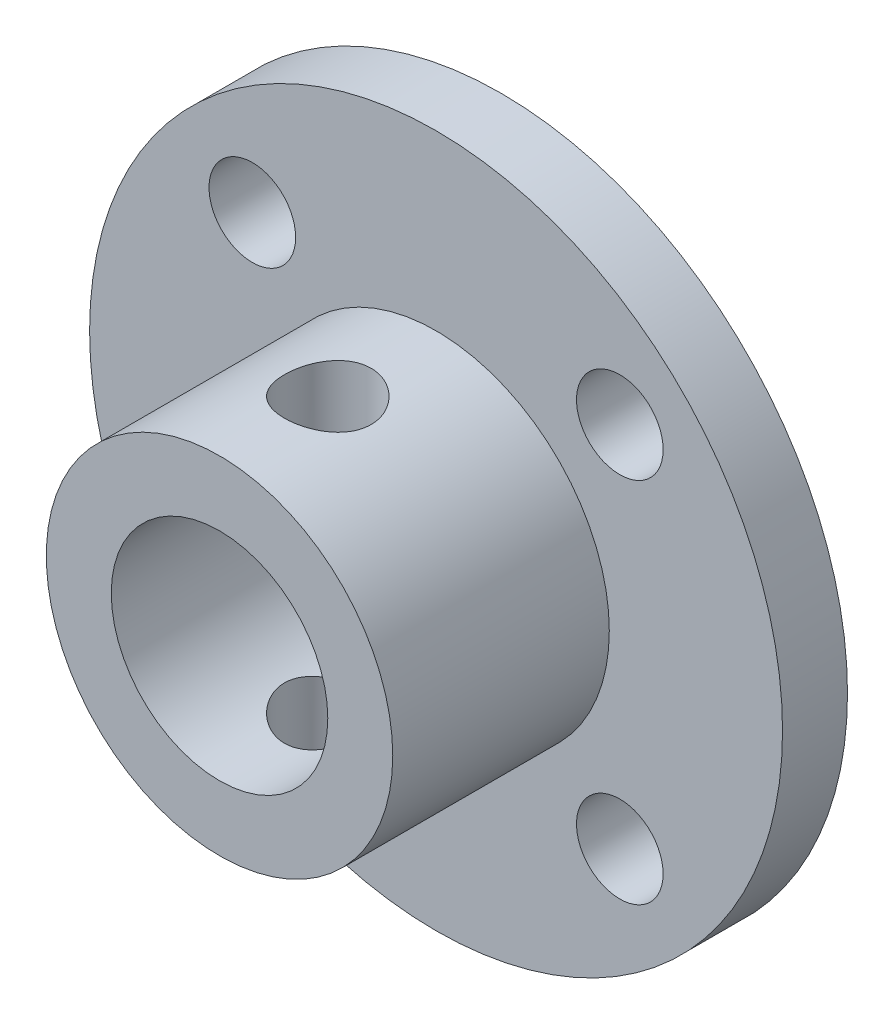
SolidWorks part; units mm, degrees
ref_plane "前视基准面" through (0, 0, 0) normal (0, 0, 1) x (1, 0, 0)
ref_plane "上视基准面" through (0, 0, 0) normal (0, 1, 0) x (1, 0, 0)
ref_plane "右视基准面" through (0, 0, 0) normal (1, 0, 0) x (0, 0, -1)
sketch "草图2" plane through (0, 0, 0) normal (0, 0, 1) x (1, 0, 0)
  circle A0 centre (0, 0) radius 16
  circle A1 centre (0, 0) radius 12 construction
  circle A2 centre (0, 0) radius 5
  circle A3 centre (8.4853, -8.4853) radius 2
  circle A4 centre (-8.4853, -8.4853) radius 2
  circle A5 centre (-8.4853, 8.4853) radius 2
  circle A6 centre (8.4853, 8.4853) radius 2
  dimension "D1" = 24
  dimension "D2" = 10
  dimension "D3" = 4
  dimension "D5" = 32
  dimension "D4" = 4
extrude "凸台-拉伸1" add sketch "草图2" along normal blind 3
sketch "草图3" plane through (0, 0, 3) normal (0, 0, 1) x (1, 0, 0)
  circle A0 centre (0, 0) radius 5
  circle A1 centre (0, 0) radius 8
  dimension "D1" = 16
extrude "凸台-拉伸2" add sketch "草图3" along normal blind 10
sketch "草图4" plane through (0, 0, 0) normal (0, 1, 0) x (1, 0, 0)
  line L0 (0, 0) -> (0, -13) construction
  line L1 (-8, -13) -> (8, -13) construction
  circle A0 centre (0, -8) radius 2
  dimension "D1" = 4
  dimension "D2" = 5
extrude "切除-拉伸1" cut sketch "草图4" against normal blind 10 and the other way blind 10
